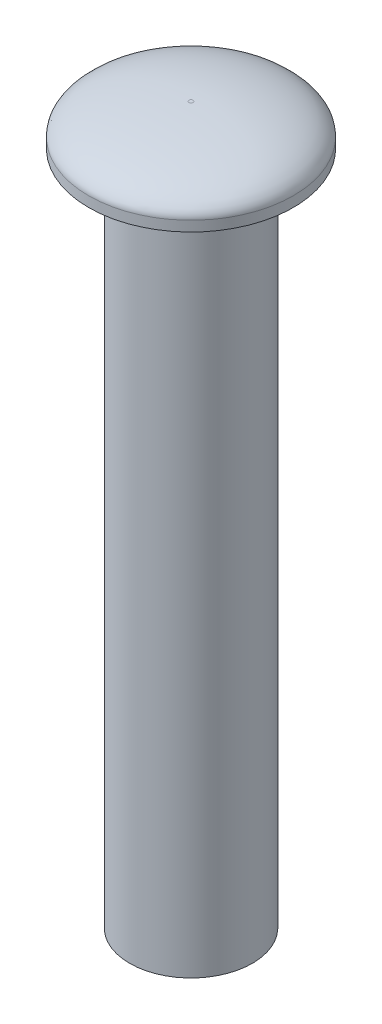
SolidWorks part; units mm, degrees
ref_plane "Front Plane" through (0, 0, 0) normal (0, 0, 1) x (1, 0, 0)
ref_plane "Top Plane" through (0, 0, 0) normal (0, 1, 0) x (1, 0, 0)
ref_plane "Right Plane" through (0, 0, 0) normal (1, 0, 0) x (0, 0, -1)
sketch "Sketch1" plane through (0, 0, 0) normal (1, 0, 0) x (0, 0, -1)
  line L0 (0, 1) -> (0, -34)
  line L1 (-5, -1) -> (5, -1)
  line L2 (-5, -1) -> (-5, 1)
  line L3 (-5, 1) -> (5, 1)
  line L4 (5, -1) -> (5, 1)
  line L5 (-5, -1) -> (5, 1) construction
  line L6 (-5, 1) -> (5, -1) construction
  line L8 (-3, -34) -> (3, -34)
  line L9 (-3, -34) -> (-3, -1)
  line L10 (-3, -1) -> (3, -1)
  line L11 (3, -34) -> (3, -1)
  line L12 (-3, -34) -> (3, -1) construction
  line L13 (-3, -1) -> (3, -34) construction
  line L14 (-2.4, -27) -> (2.4, -27)
  line L15 (-2.4, -27) -> (-2.4, -34)
  line L16 (-2.4, -34) -> (2.4, -34)
  line L17 (2.4, -27) -> (2.4, -34)
  line L18 (-2.4, -27) -> (2.4, -34) construction
  line L19 (-2.4, -34) -> (2.4, -27) construction
  point P0 (0, 0)
  point P8 (0, -17.5)
  point P14 (0, -30.5)
  dimension "D1" = 10
  dimension "D2" = 2
  dimension "D3" = 6
  dimension "D4" = 35
  dimension "D5" = 4.8
  dimension "D6" = 7
revolve "Revolve1" add sketch "Sketch1" angle 360 about L0 region at (0, 0, -2.5) region at (0, -14.8431, -1.5613)
fillet "Fillet1" radius 4.9 1 edges at (0, 1, 5) second distance 1.5 first distance on face at (0, 1, 5)
